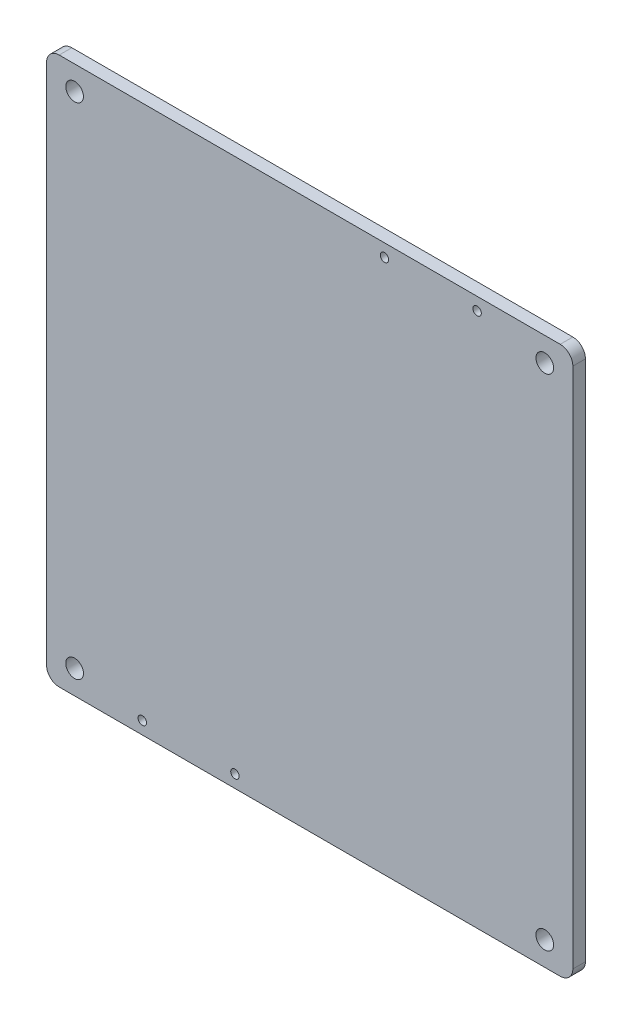
SolidWorks part; units mm, degrees
material "Thornel Mat VMA"
ref_plane "Front Plane" through (0, 0, 0) normal (0, 0, 1) x (1, 0, 0)
ref_plane "Top Plane" through (0, 0, 0) normal (0, 1, 0) x (1, 0, 0)
ref_plane "Right Plane" through (0, 0, 0) normal (1, 0, 0) x (0, 0, -1)
sketch "Sketch1" plane through (0, 0, 0) normal (0, 0, 1) x (1, 0, 0)
  line L1 (-62.5, -65) -> (62.5, -65)
  line L2 (-62.5, -65) -> (-62.5, 65)
  line L3 (-62.5, 65) -> (62.5, 65)
  line L4 (62.5, -65) -> (62.5, 65)
  line L5 (-62.5, -65) -> (62.5, 65) construction
  line L6 (-62.5, 65) -> (62.5, -65) construction
  point P0 (0, 0)
  dimension "D1" = 125
  dimension "D2" = 130
extrude "Boss-Extrude1" add sketch "Sketch1" along normal blind 3
fillet "Fillet1" radius 3 4 edges at (62.5, -65, 1.5) (-62.5, -65, 1.5) (-62.5, 65, 1.5) (62.5, 65, 1.5)
sketch "Sketch2" plane through (0, 0, 0) normal (0, 0, -1) x (-1, 0, 0)
  line L1 (-55.835, -59.325) -> (55.835, -59.325) construction
  line L2 (-55.835, -59.325) -> (-55.835, 59.325) construction
  line L3 (-55.835, 59.325) -> (55.835, 59.325) construction
  line L4 (55.835, -59.325) -> (55.835, 59.325) construction
  line L5 (-55.835, -59.325) -> (55.835, 59.325) construction
  line L6 (-55.835, 59.325) -> (55.835, -59.325) construction
  circle A0 centre (-55.835, 59.325) radius 2.1
  circle A1 centre (55.835, 59.325) radius 2.1
  circle A2 centre (-55.835, -59.325) radius 2.1
  circle A3 centre (55.835, -59.325) radius 2.1
  point P0 (0, 0)
  dimension "D1" = 118.65
  dimension "D2" = 111.67
extrude "Cut-Extrude1" cut sketch "Sketch2" against normal up to surface (3 mm away) up to face at (0, 0, 3)
sketch "Sketch3" plane through (0, 0, 0) normal (0, 0, -1) x (-1, 0, 0)
  line L0 (-62.5, 62) -> (62.5, 62) construction
  line L1 (-62.5, -62) -> (-62.5, 62) construction
  line L2 (62.5, 62) -> (62.5, -62) construction
  line L3 (-59.5, 65) -> (59.5, 65) construction
  line L4 (-62.5, -62) -> (62.5, -62) construction
  line L5 (59.5, -65) -> (-59.5, -65) construction
  circle A0 centre (-39.76, 62) radius 1
  circle A1 centre (-17.76, 62) radius 1
  circle A2 centre (39.76, -62) radius 1
  circle A3 centre (17.76, -62) radius 1
  dimension "D2" = 2
  dimension "D4" = 22
  dimension "D5" = 2
  dimension "D7" = 2
  dimension "D9" = 2
  dimension "D1" = 3
  dimension "D3" = 22.74
  dimension "D6" = 3
  dimension "D8" = 22.74
  dimension "D10" = 22
extrude "Cut-Extrude2" cut sketch "Sketch3" against normal up to surface (3 mm away) up to face at (-57.935, 59.325, 3)
